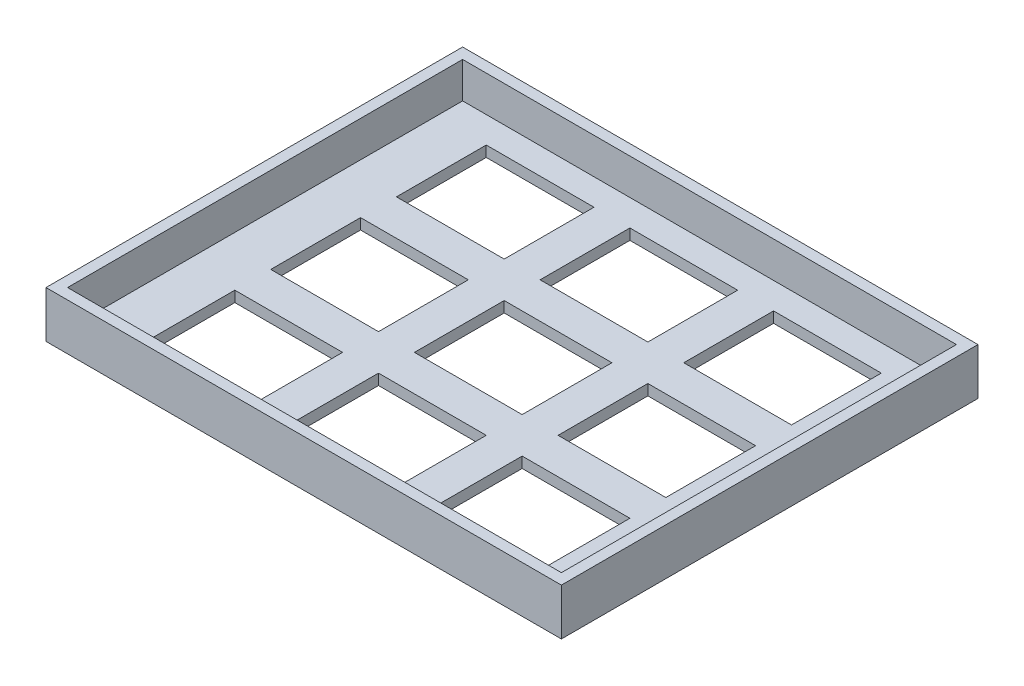
SolidWorks part; units mm, degrees
ref_plane "Front Plane" through (0, 0, 0) normal (0, 0, 1) x (1, 0, 0)
ref_plane "Top Plane" through (0, 0, 0) normal (0, 1, 0) x (1, 0, 0)
ref_plane "Right Plane" through (0, 0, 0) normal (1, 0, 0) x (0, 0, -1)
sketch "Sketch1" plane through (0, 0, 0) normal (0, 1, 0) x (1, 0, 0)
  line L1 (0, 0) -> (55, 0)
  line L2 (0, 0) -> (0, -44)
  line L3 (0, -44) -> (55, -44)
  line L4 (55, 0) -> (55, -44)
  dimension "D1" = 55
  dimension "D2" = 44
extrude "Boss-Extrude1" add sketch "Sketch1" along normal blind 4
shell "Shell1" thickness 1.2 removed face at (27.5, 4, 22) outward yes
sketch "Sketch2" plane through (0, 0, 0) normal (0, 1, 0) x (1, 0, 0)
  line L0 (33.5701, -40.9392) -> (33.5701, -30.9392)
  line L1 (49.5701, -40.9392) -> (37.5701, -40.9392)
  line L2 (49.5701, -40.9392) -> (49.5701, -30.9392)
  line L3 (49.5701, -30.9392) -> (37.5701, -30.9392)
  line L4 (37.5701, -40.9392) -> (37.5701, -30.9392)
  line L5 (33.5701, -40.9392) -> (21.5701, -40.9392)
  line L6 (21.5701, -40.9392) -> (21.5701, -30.9392)
  line L7 (33.5701, -30.9392) -> (21.5701, -30.9392)
  line L8 (17.5701, -40.9392) -> (17.5701, -30.9392)
  line L9 (17.5701, -40.9392) -> (5.5701, -40.9392)
  line L10 (5.5701, -40.9392) -> (5.5701, -30.9392)
  line L11 (17.5701, -30.9392) -> (5.5701, -30.9392)
  line L12 (33.5701, -26.9392) -> (33.5701, -16.9392)
  line L13 (33.5701, -26.9392) -> (21.5701, -26.9392)
  line L14 (21.5701, -26.9392) -> (21.5701, -16.9392)
  line L15 (33.5701, -16.9392) -> (21.5701, -16.9392)
  line L16 (17.5701, -26.9392) -> (17.5701, -16.9392)
  line L17 (17.5701, -26.9392) -> (5.5701, -26.9392)
  line L18 (5.5701, -26.9392) -> (5.5701, -16.9392)
  line L19 (17.5701, -16.9392) -> (5.5701, -16.9392)
  line L20 (33.5701, -12.9392) -> (33.5701, -2.9392)
  line L21 (33.5701, -12.9392) -> (21.5701, -12.9392)
  line L22 (21.5701, -12.9392) -> (21.5701, -2.9392)
  line L23 (33.5701, -2.9392) -> (21.5701, -2.9392)
  line L24 (17.5701, -12.9392) -> (17.5701, -2.9392)
  line L25 (17.5701, -12.9392) -> (5.5701, -12.9392)
  line L26 (5.5701, -12.9392) -> (5.5701, -2.9392)
  line L27 (17.5701, -2.9392) -> (5.5701, -2.9392)
  line L28 (49.5701, -26.9392) -> (49.5701, -16.9392)
  line L29 (49.5701, -26.9392) -> (37.5701, -26.9392)
  line L30 (37.5701, -26.9392) -> (37.5701, -16.9392)
  line L31 (49.5701, -16.9392) -> (37.5701, -16.9392)
  line L32 (49.5701, -12.9392) -> (49.5701, -2.9392)
  line L33 (49.5701, -12.9392) -> (37.5701, -12.9392)
  line L34 (37.5701, -12.9392) -> (37.5701, -2.9392)
  line L35 (49.5701, -2.9392) -> (37.5701, -2.9392)
  dimension "D1" = 12
  dimension "D2" = 10
  dimension "D3" = 3
  dimension "D4" = 3
extrude "Cut-Extrude2" cut sketch "Sketch2" against normal through all
